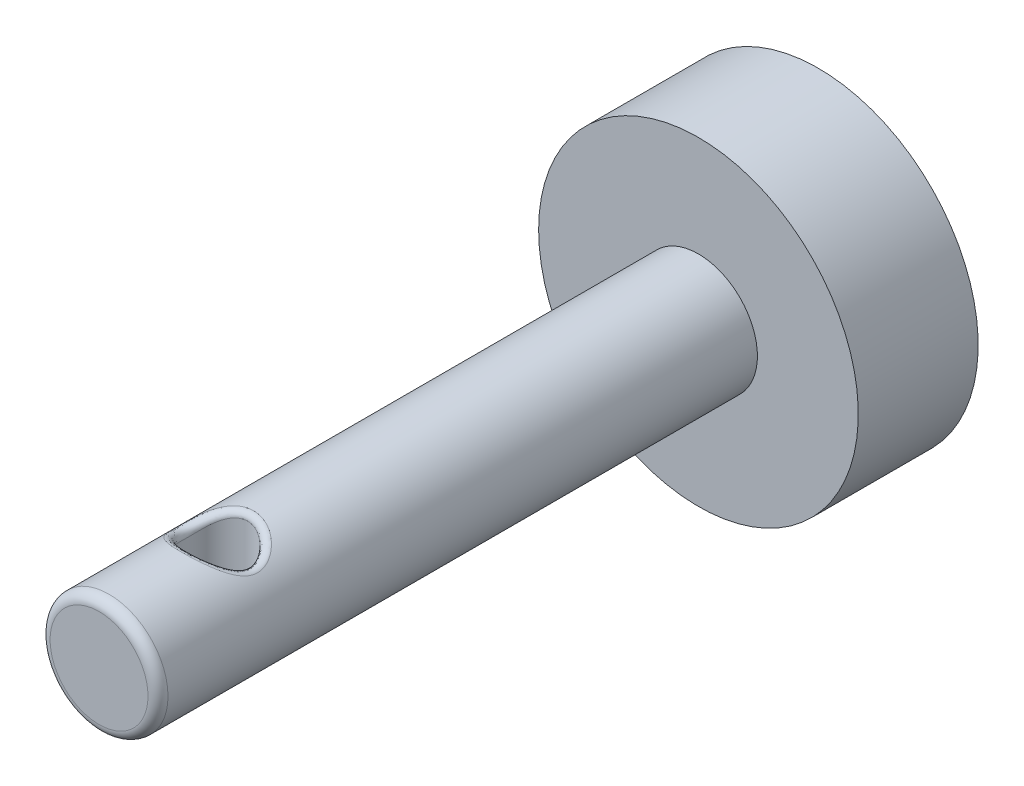
SolidWorks part; units mm, degrees
material "Alloy Steel"
ref_plane "Front Plane" through (0, 0, 0) normal (0, 0, 1) x (1, 0, 0)
ref_plane "Top Plane" through (0, 0, 0) normal (0, 1, 0) x (1, 0, 0)
ref_plane "Right Plane" through (0, 0, 0) normal (1, 0, 0) x (0, 0, -1)
sketch "Sketch1" plane through (0, 0, 0) normal (0, 0, 1) x (1, 0, 0)
  circle A0 centre (0, 0) radius 2.95
  dimension "D1" = 5.9
extrude "Boss-Extrude1" add sketch "Sketch1" along normal blind 40
fillet "Fillet1" radius 0.6 1 edges at (2.95, 0, 40)
sketch "Sketch2" plane through (0, 0, 0) normal (0, 0, -1) x (-1, 0, 0)
  circle A0 centre (0, 0) radius 8
extrude "Boss-Extrude2" add sketch "Sketch2" against normal blind 6
sketch "Sketch3" plane through (0, 0, 0) normal (0, 1, 0) x (1, 0, 0)
  circle A0 centre (0, -30.0653) radius 1.5
  dimension "D1" = 3
extrude "Cut-Extrude1" cut sketch "Sketch3" against normal blind 6 and the other way blind 6
fillet "Fillet2" radius 0.3 2 edges at (-0.1452, -2.9464, 31.5582) (0.1452, 2.9464, 31.5582)
sketch "Sketch4" plane through (0, 0, 40) normal (0, 0, 1) x (1, 0, 0)
  circle A0 centre (0, 0) radius 7.4154
extrude "Cut-Extrude2" cut sketch "Sketch4" against normal blind 4
fillet "Fillet3" radius 0.5 1 edges at (2.95, 0, 36)
ref_axis "Axis1" through (0, 0, 6) along (0, 0, -1)
